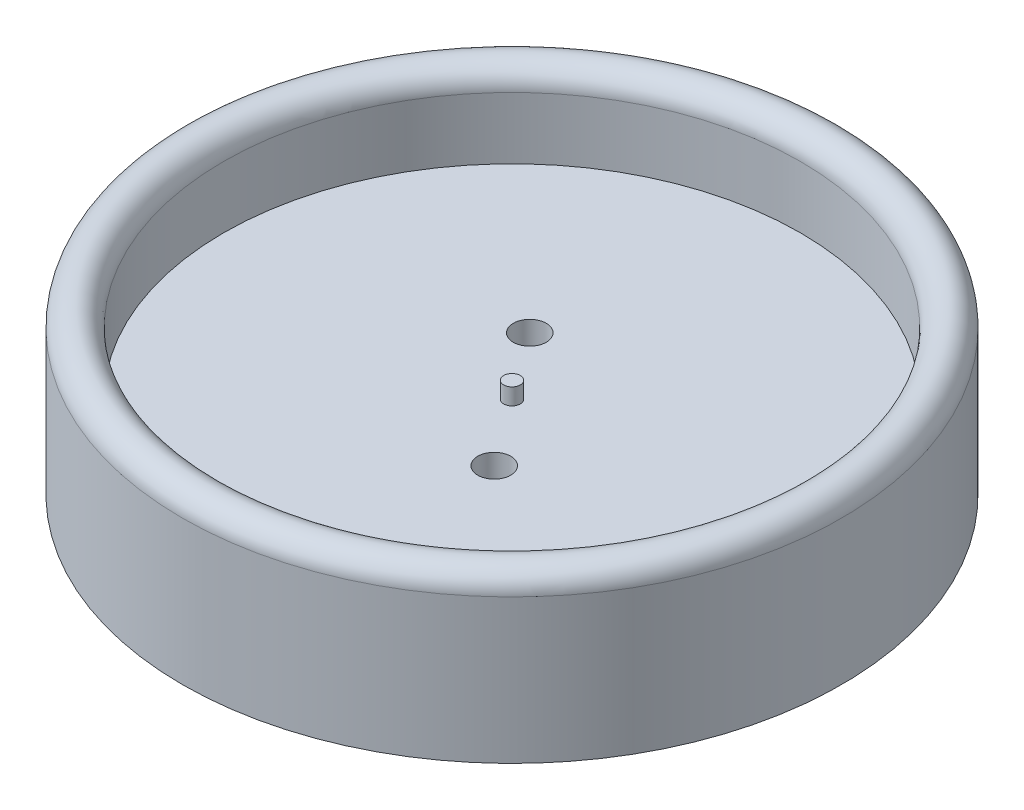
SolidWorks part; units mm, degrees
ref_plane "前基準面" through (0, 0, 0) normal (0, 0, 1) x (1, 0, 0)
ref_plane "上基準面" through (0, 0, 0) normal (0, 1, 0) x (1, 0, 0)
ref_plane "右基準面" through (0, 0, 0) normal (1, 0, 0) x (0, 0, -1)
sketch "草圖1" plane through (0, 0, 0) normal (0, 1, 0) x (1, 0, 0)
  circle A0 centre (0, 0) radius 40
  dimension "D1" = 80
extrude "填料-伸長1" add sketch "草圖1" along normal blind 10
sketch "草圖2" plane through (0, 10, 0) normal (0, 1, 0) x (1, 0, 0)
  circle A0 centre (0, 0) radius 40
  circle A1 centre (0, 0) radius 35
  dimension "D1" = 80
  dimension "D2" = 70
extrude "填料-伸長2" add sketch "草圖2" along normal blind 10
sketch "草圖3" plane through (0, 0, 0) normal (0, -1, 0) x (1, 0, 0)
  line L0 (15.2364, 20.7944) -> (-15.2364, -20.7944) construction
  circle A0 centre (5.9104, 8.0664) radius 2
  circle A1 centre (-5.9104, -8.0664) radius 2
  dimension "D1" = 4
  dimension "D2" = 10
  dimension "D3" = 10
extrude "除料-伸長1" cut sketch "草圖3" against normal blind 20
sketch "草圖4" plane through (0, 0, 0) normal (0, -1, 0) x (1, 0, 0)
  circle A0 centre (5.9104, 8.0664) radius 5
  circle A1 centre (-5.9104, -8.0664) radius 5
  dimension "D1" = 10
extrude "除料-伸長2" cut sketch "草圖4" against normal blind 3
fillet "圓角1" radius 1.5 2 edges at (-5.9104, 3, -10.0664) (-5.9104, 3, -13.0664)
fillet "圓角2" radius 1.5 2 edges at (5.9104, 3, 6.0664) (5.9104, 3, 3.0664)
fillet "圓角3" 2 edges at (0, 20, 40) (0, 20, 35) type full round first side face at (0, 0, 40) second side face at (0, 20, 35) middle face at (0, 20, 40)
sketch "草圖5" plane through (0, 10, 0) normal (0, 1, 0) x (1, 0, 0)
  circle A0 centre (0, 0) radius 1
  dimension "D1" = 2
extrude "填料-伸長3" add sketch "草圖5" along normal blind 2
